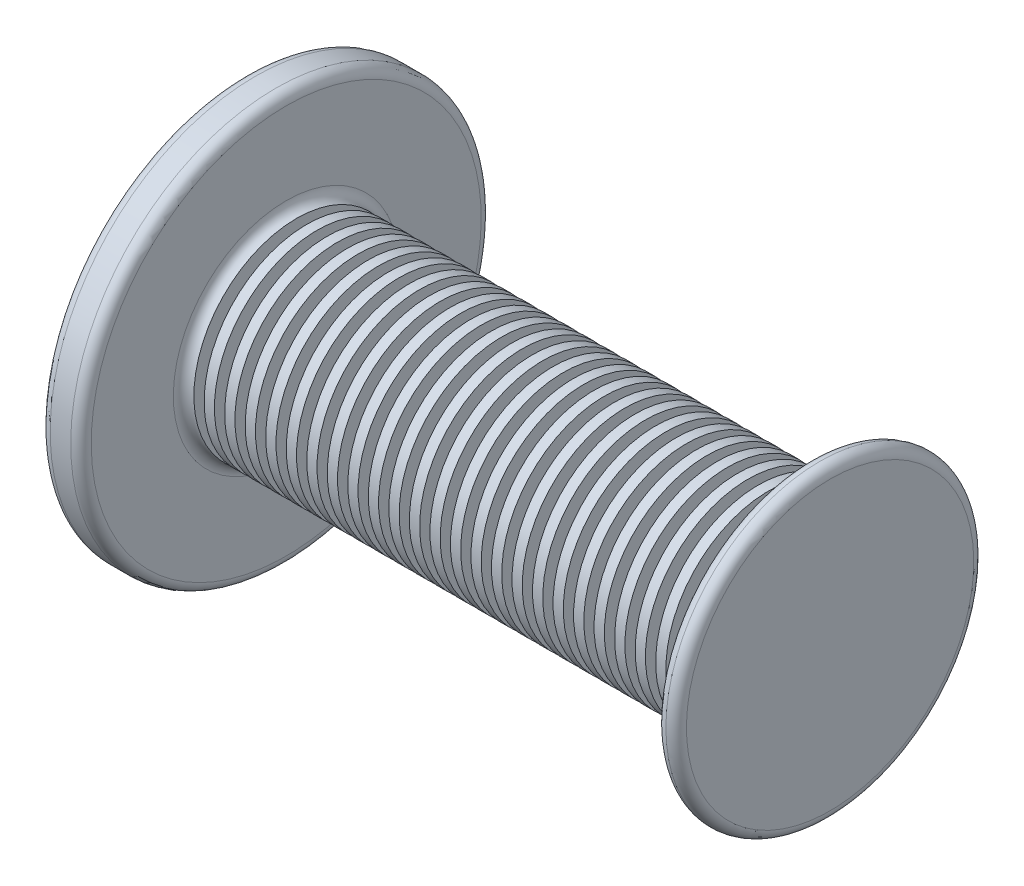
SolidWorks part; units mm, degrees
material "Silicon Rubber"
ref_plane "Front Plane" through (0, 0, 0) normal (0, 0, 1) x (1, 0, 0)
ref_plane "Top Plane" through (0, 0, 0) normal (0, 1, 0) x (1, 0, 0)
ref_plane "Right Plane" through (0, 0, 0) normal (1, 0, 0) x (0, 0, -1)
sketch "Sketch1" plane through (0, 0, 0) normal (0, 0, 1) x (1, 0, 0)
  line L0 (0, 0) -> (0, 20)
  line L1 (0, 20) -> (4, 20)
  line L2 (4, 20) -> (4, 10)
  line L3 (4, 10) -> (55, 10)
  line L4 (55, 10) -> (55, 15)
  line L5 (55, 15) -> (57, 15)
  line L6 (57, 15) -> (57, 0)
  line L7 (57, 0) -> (0, 0)
  point P11 (0, 10)
  dimension "D1" = 55
  dimension "D2" = 2
  dimension "D3" = 20
  dimension "D4" = 4
  dimension "D5" = 15
revolve "Revolve2" add sketch "Sketch1" angle 360 about L7
fillet "Fillet1" radius 1 2 edges at (55, 15, 0) (57, 15, 0)
fillet "Fillet2" radius 1 2 edges at (0, 20, 0) (4, 20, 0)
fillet "Fillet3" radius 1 2 edges at (55, 10, 0) (4, 10, 0)
ref_plane "Plane2" through (5, 0, 0) normal (1, 0, 0) x (0, 0, -1)
sketch "Sketch3" plane through (5, 0, 0) normal (1, 0, 0) x (0, 0, -1)
  circle A0 centre (0, 0) radius 7.5
  circle A1 centre (0, 0) radius 10
  dimension "D1" = 15
  dimension "D2" = 20
extrude "Cut-Extrude12" cut sketch "Sketch3" along normal blind 1
pattern_linear "LPattern1" count 25 spacing 2 along (1, 0, 0) of "Cut-Extrude12"
sketch "Sketch5" plane through (0, 0, 0) normal (-1, 0, 0) x (0, 0, 1)
  circle A0 centre (0, 0) radius 5
  dimension "D1" = 10
extrude "Cut-Extrude13" cut sketch "Sketch5" against normal blind 55
